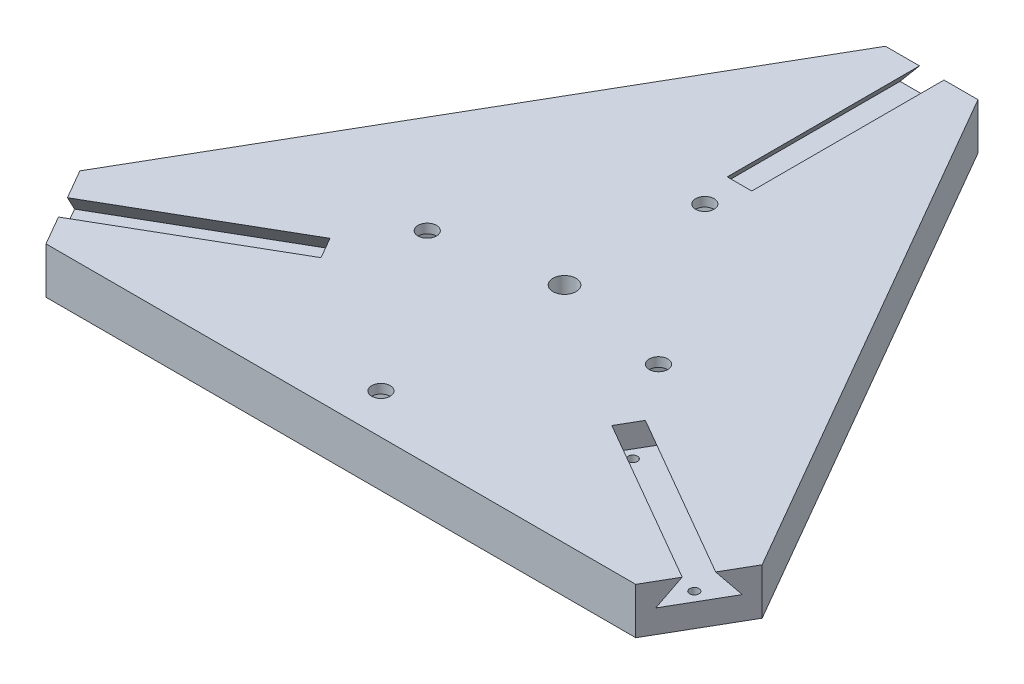
SolidWorks part; units mm, degrees
material "PLA"
ref_plane "Plan de face" through (0, 0, 0) normal (0, 0, 1) x (1, 0, 0)
ref_plane "Plan de dessus" through (0, 0, 0) normal (0, 1, 0) x (1, 0, 0)
ref_plane "Plan de droite" through (0, 0, 0) normal (1, 0, 0) x (0, 0, -1)
sketch "Esquisse1" plane through (0, 0, 0) normal (0, 1, 0) x (1, 0, 0)
  line L29 (-10, 79.3725) -> (10, 79.3725)
  line L30 (73.7386, -31.026) -> (63.7386, -48.3465)
  line L31 (-63.7386, -48.3465) -> (-73.7386, -31.026)
  line L32 (-10, 79.3725) -> (-73.7386, -31.026)
  line L33 (-63.7386, -48.3465) -> (63.7386, -48.3465)
  line L34 (73.7386, -31.026) -> (10, 79.3725)
  circle A7 centre (0, 0) radius 2.5
  circle A8 centre (0, 0) radius 79.3725 construction
  point P17 (0, 0)
  dimension "D1" = 20
  dimension "D4" = 20
  dimension "D5" = 80
  dimension "D6" = 80
  dimension "D3" = 80
  dimension "D9" = 5
  dimension "D12" = 79.3725
  dimension "D2" = 20
  dimension "D7" = 60
  dimension "D8" = 60
  dimension "D10" = 80
  dimension "D11" = 80
extrude "Boss.-Extru.1" add sketch "Esquisse1" along normal mid plane 10
sketch "Esquisse2" plane through (0, 5, 0) normal (0, 1, 0) x (1, 0, 0)
  line L0 (-68.7386, -39.6863) -> (0, 0) construction
  line L1 (-73.7386, -31.026) -> (-63.7386, -48.3465) construction
  circle A0 centre (-66.3571, -38.3113) radius 1
  circle A1 centre (-34.9203, -20.1613) radius 1
  dimension "D1" = 2
  dimension "D4" = 2
  dimension "D2" = 2.75
  dimension "D3" = 39.05
extrude "Enlèv. mat.-Extru.1" cut sketch "Esquisse2" against normal through all
pattern_circular "Répétition circulaire1" count 3 over 360 about axis through (0, 5, 0) along (0, -1, 0) of "Enlèv. mat.-Extru.1" reverse direction yes
sketch "Esquisse3" plane through (68.7386, 0, 39.6863) normal (0.866, 0, 0.5) x (0.5, 0, -0.866)
  line L0 (2.65, 5) -> (6.845, 0)
  line L1 (-10, 5) -> (10, 5) construction
  line L3 (-6.845, 0) -> (-2.65, 5)
  line L4 (-2.65, 5) -> (2.65, 5)
  line L6 (-6.845, 0) -> (6.845, 0)
  point P6 (0, 5)
  point P11 (0, 0)
  dimension "D1" = 5.3
  dimension "D2" = 13.69
extrude "Enlèv. mat.-Extru.2" cut sketch "Esquisse3" against normal blind 41.553
pattern_circular "Répétition circulaire2" count 3 over 360 about axis through (0, 5, 0) along (0, -1, 0) of "Enlèv. mat.-Extru.2"
sketch "Esquisse4" plane through (0, -5, 0) normal (0, -1, 0) x (1, 0, 0)
  line L0 (0, 0) -> (25, 0) construction
  line L1 (25, 0) -> (25, 4.68) construction
  line L2 (0, 0) -> (-25, 0) construction
  line L3 (-25, 0) -> (-25, 4.68) construction
  circle A3 centre (0, -30.3225) radius 2
  circle A4 centre (0, -40.3225) radius 1 construction
  circle A7 centre (0, 39.68) radius 2
  circle A8 centre (25, 4.68) radius 2
  circle A9 centre (-25, 4.68) radius 2
  point P7 (0, 0)
  point P15 (0, 0)
  dimension "D3" = 25
  dimension "D4" = 4.68
  dimension "D7" = 4
  dimension "D8" = 39.68
  dimension "D1" = 10
  dimension "D2" = 4
  dimension "D5" = 25
  dimension "D9" = 4
  dimension "D10" = 4
  dimension "D6" = 4.68
extrude "Enlèv. mat.-Extru.3" cut sketch "Esquisse4" against normal through all
sketch "Esquisse5" plane through (0, -5, 0) normal (0, -1, 0) x (1, 0, 0)
  line L0 (-19.85, 34.53) -> (19.85, 34.53)
  line L1 (-19.85, 34.53) -> (-19.85, -25.1725)
  line L2 (-19.85, -25.1725) -> (19.85, -25.1725)
  line L3 (19.85, -25.1725) -> (19.85, 34.53)
  line L4 (-30.15, 44.83) -> (30.15, 44.83)
  line L5 (30.15, -35.4725) -> (30.15, 44.83)
  line L6 (-30.15, -35.4725) -> (30.15, -35.4725)
  line L7 (-30.15, 44.83) -> (-30.15, -35.4725)
  circle A0 centre (25, 4.68) radius 2 construction
  circle A1 centre (-25, 4.68) radius 2 construction
  circle A2 centre (0, 39.68) radius 2 construction
  circle A3 centre (0, -30.3225) radius 2 construction
  dimension "D1" = 5.15
  dimension "D2" = 5.15
  dimension "D3" = 5.15
  dimension "D4" = 5.15
  dimension "D5" = 10.3
extrude "Enlèv. mat.-Extru.4" cut sketch "Esquisse5" against normal blind 8
sketch "Esquisse6" plane through (0, -5, 0) normal (0, -1, 0) x (1, 0, 0)
  line L4 (19.85, 34.53) -> (-19.85, 34.53) construction
  circle A0 centre (0, 20.18) radius 3.325
  circle A1 centre (0, 20.18) radius 6.325
  dimension "D2" = 6.65
  dimension "D3" = 3
  dimension "D1" = 14.35
extrude "Boss.-Extru.2" add sketch "Esquisse6" along normal blind 10
